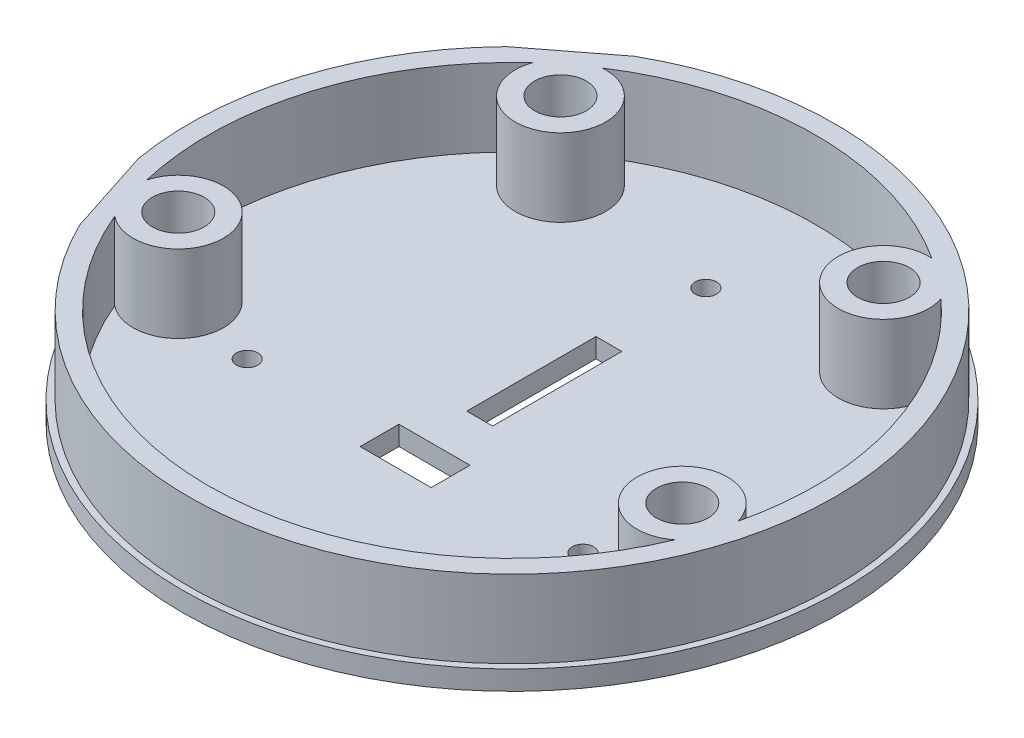
SolidWorks part; units mm, degrees
material "3.0205 (EN-AW 1200)"
ref_plane "Спереди" through (0, 0, 0) normal (0, 0, 1) x (1, 0, 0)
ref_plane "Сверху" through (0, 0, 0) normal (0, 1, 0) x (1, 0, 0)
ref_plane "Справа" through (0, 0, 0) normal (1, 0, 0) x (0, 0, -1)
other "Configuration Table"
sketch "Эскиз1" plane through (0, 0, 0) normal (0, 1, 0) x (1, 0, 0)
  circle A0 centre (0, 0) radius 51
  dimension "D1" = 102
extrude "Бобышка-Вытянуть1" add sketch "Эскиз1" along normal blind 3
sketch "Эскиз2" plane through (0, 3, 0) normal (0, 1, 0) x (1, 0, 0)
  circle A0 centre (0, 0) radius 50
  circle A1 centre (0, 0) radius 47
  circle A2 centre (0, 0) radius 51
  circle A3 centre (0, 0) radius 51
  dimension "D2" = 100
  dimension "D3" = 94
  dimension "D1" = 0
extrude "Бобышка-Вытянуть2" add sketch "Эскиз2" along normal blind 12 contours A0 A1 region at (-48.5858, 3, 0)
sketch "Эскиз5" plane through (0, 3, 0) normal (0, 1, 0) x (1, 0, 0)
  line L0 (0, 0) -> (50000, 0) construction
  line L1 (0, 0) -> (0, 50000) construction
  circle A0 centre (0, 0) radius 30 construction
  circle A1 centre (0, 30) radius 1.65
  dimension "D1" = 60
  dimension "D2" = 3.3
extrude "Вырез-Вытянуть1" cut sketch "Эскиз5" against normal blind 10
pattern_circular "Круговой массив1" count 3 over 360 about axis through (0, 15, 0) along (0, -1, 0) of "Вырез-Вытянуть1" reverse direction yes
sketch "Эскиз6" plane through (0, 3, 0) normal (0, 1, 0) x (1, 0, 0)
  line L0 (0, -1000) -> (0, 49000) construction
  line L1 (-1025.9808, -15) -> (48974.0192, -15) construction
  line L2 (-2, -5) -> (2, -5)
  line L3 (-2, -5) -> (-2, 15)
  line L4 (-2, 15) -> (2, 15)
  line L5 (2, -5) -> (2, 15)
  line L6 (-2, -5) -> (2, 15) construction
  line L7 (-2, 15) -> (2, -5) construction
  line L8 (-5.5, -12) -> (5.5, -12)
  line L9 (-5.5, -12) -> (-5.5, -18)
  line L10 (-5.5, -18) -> (5.5, -18)
  line L11 (5.5, -12) -> (5.5, -18)
  line L12 (-5.5, -12) -> (5.5, -18) construction
  line L13 (-5.5, -18) -> (5.5, -12) construction
  circle A1 centre (0, 30) radius 1.65 construction
  point P1 (0, 5)
  point P10 (0, -15)
  dimension "D3" = 15
  dimension "D1" = 4
  dimension "D2" = 20
  dimension "D4" = 6
  dimension "D5" = 11
extrude "Вырез-Вытянуть2" cut sketch "Эскиз6" against normal blind 10
sketch "Эскиз7" plane through (0, 3, 0) normal (0, 1, 0) x (1, 0, 0)
  line L0 (-1000, 0) -> (49000, 0) construction
  line L1 (0, -1000) -> (0, 49000) construction
  line L2 (-39, -12.6491) -> (39, -12.6491) construction
  line L3 (-25, 32.4962) -> (25, 32.4962) construction
  circle A0 centre (0, 0) radius 41 construction
  circle A1 centre (-39, -12.6491) radius 4
  circle A2 centre (39, -12.6491) radius 4
  circle A3 centre (-39, -12.6491) radius 7
  circle A4 centre (39, -12.6491) radius 7
  circle A5 centre (-25, 32.4962) radius 4
  circle A6 centre (25, 32.4962) radius 4
  circle A7 centre (-25, 32.4962) radius 7
  circle A8 centre (25, 32.4962) radius 7
  dimension "D1" = 82
  dimension "D2" = 8
  dimension "D3" = 8
  dimension "D5" = 14
  dimension "D6" = 14
  dimension "D7" = 8
  dimension "D8" = 8
  dimension "D10" = 14
  dimension "D11" = 14
  dimension "D4" = 78
  dimension "D9" = 50
extrude "Бобышка-Вытянуть3" add sketch "Эскиз7" along normal blind 12
sketch "Эскиз8" plane through (0, 15, 0) normal (0, 1, 0) x (1, 0, 0)
  line L0 (0, 0) -> (-39, -12.6491) construction
  line L1 (-49.2614, -8.5622) -> (-44.9093, -21.9808)
  line L2 (0, 0) -> (-25, 32.4962) construction
  line L3 (-35.7733, 34.9323) -> (-24.5925, 43.534)
  circle A1 centre (0, 0) radius 50 construction
  arc A2 (-24.5925, 43.534) -> (-35.7733, 34.9323) centre (0, 0) ccw
  arc A3 (-49.2614, -8.5622) -> (-44.9093, -21.9808) centre (0, 0) ccw
  dimension "D1" = 49.5
  dimension "D2" = 49.5
extrude "Вырез-Вытянуть3" cut sketch "Эскиз8" against normal blind 12
